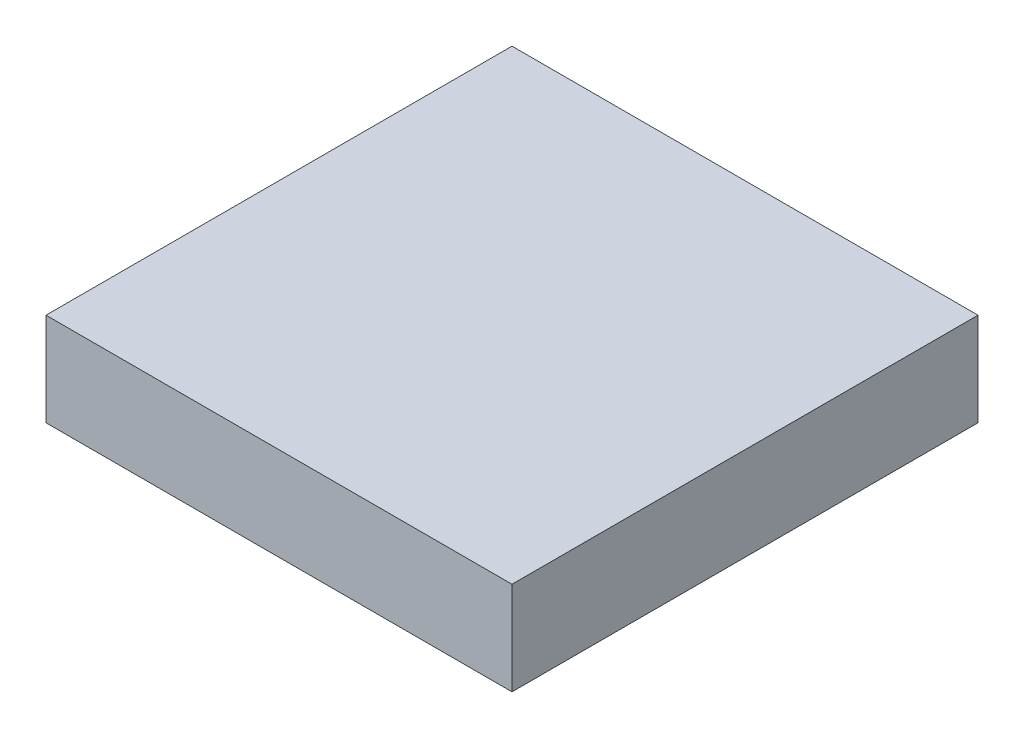
SolidWorks part; units mm, degrees
ref_plane "Front Plane" through (0, 0, 0) normal (0, 0, 1) x (1, 0, 0)
ref_plane "Top Plane" through (0, 0, 0) normal (0, 1, 0) x (1, 0, 0)
ref_plane "Right Plane" through (0, 0, 0) normal (1, 0, 0) x (0, 0, -1)
sketch "Sketch1" plane through (0, 0, 0) normal (0, 1, 0) x (1, 0, 0)
  line L0 (5, 10) -> (5, 0)
  line L1 (0, 0) -> (10, 0)
  line L2 (0, 0) -> (0, 10)
  line L3 (0, 10) -> (10, 10)
  line L4 (10, 0) -> (10, 10)
  line L5 (1, 9) -> (9, 9)
  line L6 (1, 9) -> (1, 1)
  line L7 (1, 1) -> (9, 1)
  line L8 (9, 9) -> (9, 1)
  line L10 (10, 10) -> (7.5, 10)
  line L11 (10, 10) -> (10, 7.5)
  line L12 (10, 7.5) -> (7.5, 7.5)
  line L13 (7.5, 10) -> (7.5, 7.5)
  circle A0 centre (5, 5) radius 2.0355
  circle A1 centre (7.5, 7.5) radius 1.5
  circle A2 centre (5, 5) radius 1.5
  point P9 (5, 9)
  point P10 (5, 10)
  point P11 (1, 5)
  point P12 (0, 5)
  dimension "D4" = 3
  dimension "D1" = 10
  dimension "D2" = 8
  dimension "D3" = 2.5
extrude "Boss-Extrude1" add sketch "Sketch1" along normal blind 1 contours L7 L6 L5 L0 L3 L2 L1 | A0 L0 L5 L6 L7 | A2 L0 A0 | L0 A2 | L0 A2 | A2 L0 A0 | A1 L5 L0 A0 | L13 L3 L0 L5 | L3 L13 L5 L8 L12 L4 | A1 L8 L5 | L13 A1 L12 | L12 A1 L13 | A1 A0 L0 L7 L8 | L4 L12 L8 L7 L0 L1 region at (6.25, 0, -9.5) region at (4.8882, 0, -9.5) region at (5.6784, 0, -8.0747) region at (2.7099, 0, -5) region at (9.0312, 0, -9.0312) region at (5.7615, 0, -6.8385) region at (4.9545, 0, -6.7678) region at (8.1366, 0, -8.1366) region at (8.6649, 0, -8.6649) region at (7.2878, 0, -7.2878) region at (5.6366, 0, -5) region at (4.3634, 0, -5) region at (7.4229, 0, -3.2124) region at (9.5, 0, -7.4099)
extrude "Boss-Extrude3" add sketch "Sketch1<4>" against normal blind 1 contours A2 L0 A0 | A2 L0 A0 | L7 L6 L5 L0 L3 L2 L1 | L4 L12 L8 L7 L0 L1 | L3 L13 L5 L8 L12 L4 | L13 L3 L0 L5 region at (6.25, 0, -9.5) region at (4.8882, 0, -9.5) region at (9.0312, 0, -9.0312) region at (5.7615, 0, -6.8385) region at (4.9545, 0, -6.7678) region at (9.5, 0, -7.4099)
sketch "Sketch1<4>" plane through (0, 0, 0) normal (0, 1, 0) x (1, 0, 0) same geometry as "Sketch1"
